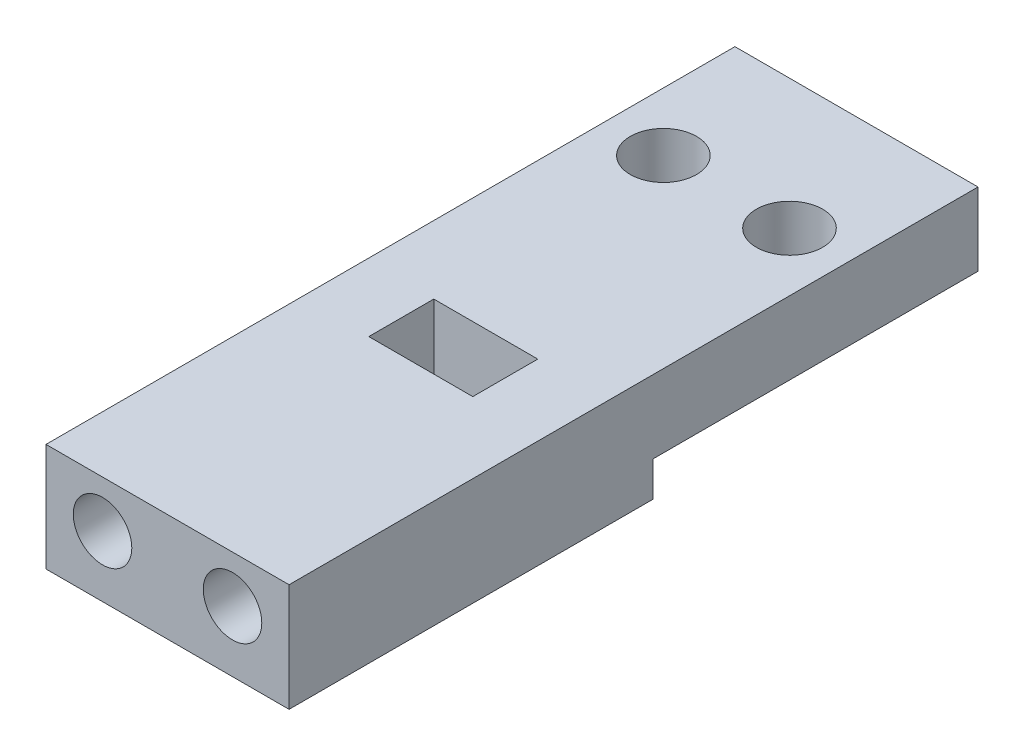
SolidWorks part; units mm, degrees
ref_plane "前视基准面" through (0, 0, 0) normal (0, 0, 1) x (1, 0, 0)
ref_plane "上视基准面" through (0, 0, 0) normal (0, 1, 0) x (1, 0, 0)
ref_plane "右视基准面" through (0, 0, 0) normal (1, 0, 0) x (0, 0, -1)
other "Configuration Table"
sketch "草图1" plane through (0, 0, 0) normal (0, 0, 1) x (1, 0, 0)
  line L1 (-11.1667, -5) -> (11.1667, -5)
  line L2 (-11.1667, -5) -> (-11.1667, 5)
  line L3 (-11.1667, 5) -> (11.1667, 5)
  line L4 (11.1667, -5) -> (11.1667, 5)
  line L5 (-11.1667, -5) -> (11.1667, 5) construction
  line L6 (-11.1667, 5) -> (11.1667, -5) construction
  point P0 (0, 0)
  dimension "D1" = 10
extrude "凸台-拉伸1" add sketch "草图1" along normal blind 30
sketch "草图2" plane through (0, -5, 0) normal (0, -1, 0) x (1, 0, 0)
  line L0 (-10.0833, 30.4566) -> (-10.0833, 0)
  line L1 (-10.0833, 30) -> (-10.0833, 38.1808) construction
  line L2 (-11.1667, 0) -> (11.1667, 0) construction
sketch "草图3" plane through (0, 0, 30) normal (0, 0, 1) x (1, 0, 0)
  line L0 (-9.2333, 0.05) -> (-9.2333, -5.0113)
  line L2 (9.4667, -5) -> (9.4667, 0.05)
  circle A0 centre (5.1167, -0.3) radius 2.25
  circle A1 centre (-4.8833, -0.3) radius 2.25
  arc A3 (9.4667, 0.05) -> (7.4667, 2.05) centre (7.4667, 0.05) ccw
  arc A4 (-9.2333, 0.05) -> (-6.4511, 1.8907) centre (-7.2333, 0.05) cw
sketch "草图4" plane through (0, -5, 0) normal (0, -1, 0) x (1, 0, 0)
  line L1 (-11.1667, 30) -> (-10.0833, 30)
  line L2 (-11.1667, 30) -> (-11.1667, 0)
  line L3 (-11.1667, 0) -> (-10.0833, 0)
  line L4 (-10.0833, 30) -> (-10.0833, 0)
extrude "切除-拉伸1" cut sketch "草图4" against normal blind 30
extrude "切除-拉伸2" cut sketch "草图3" against normal blind 15 contours A1 | A0 region at (-4.8833, -0.3, 30)
sketch "草图5" plane through (0, 0, 30) normal (0, 0, 1) x (1, 0, 0)
  line L0 (9.4667, -5) -> (9.4667, 0.05) construction
  line L1 (-9.2333, -5.0113) -> (9.4667, -5.0113)
  line L2 (-9.2333, -5.0113) -> (-9.2333, 3.3044)
  line L3 (-9.2333, 3.3044) -> (9.4667, 3.3044)
  line L4 (9.4667, -5.0113) -> (9.4667, 3.3044)
extrude "切除-拉伸3" cut sketch "草图5" against normal blind 30 flip side to cut
sketch "草图6" plane through (9.4667, 0, 0) normal (1, 0, 0) x (0, 0, -1)
  line L0 (22.3266, -2.313) -> (13.2059, -2.313) construction
sketch "草图7" plane through (0, 3.3044, 0) normal (0, 1, 0) x (1, 0, 0)
  arc A0 (-18.3547, 13) -> (-15.8066, 10.45) centre (-15.8066, 12.9981) cw
sketch "草图10" plane through (0, 0, 0) normal (0, 0, -1) x (-1, 0, 0)
  line L4 (-9.4667, -5) -> (9.2333, -5)
  line L5 (9.2333, -5) -> (9.2333, 3.3044)
  line L6 (9.2333, 3.3044) -> (-9.4667, 3.3044)
  line L7 (-9.4667, 3.3044) -> (-9.4667, -5)
  line L8 (-9.4667, -5) -> (9.2333, -5)
  line L9 (9.2333, -5) -> (9.2333, 3.3044)
  line L10 (9.2333, 3.3044) -> (-9.4667, 3.3044)
  line L11 (-9.4667, 3.3044) -> (-9.4667, -5)
  dimension "D1" = 0
extrude "凸台-拉伸2" add sketch "草图10" along normal blind 18
sketch "草图11" plane through (9.4667, 0, 0) normal (1, 0, 0) x (0, 0, -1)
  line L1 (18, -5) -> (-2, -5)
  line L2 (18, -5) -> (18, -2.313)
  line L3 (18, -2.313) -> (-2, -2.313)
  line L4 (-2, -5) -> (-2, -2.313)
  dimension "D1" = 20
extrude "切除-拉伸5" cut sketch "草图11" against normal through all
sketch "草图12" plane through (0, -2.313, 0) normal (0, -1, 0) x (1, 0, 0)
  line L0 (-9.2333, -12.9981) -> (9.4667, -12.9981)
  line L1 (-9.2333, -18) -> (-9.2333, 2) construction
  line L2 (9.4667, -200022.3266) -> (9.4667, 199986.7941) construction
  circle A0 centre (-4.7333, -12.9981) radius 2.5481
  circle A1 centre (4.9667, -12.9981) radius 2.5481
  point P5 (-4.7333, -12.9981)
  point P8 (4.9667, -12.9981)
  point P11 (0.1167, -12.9981)
  dimension "D1" = 4.5
  dimension "D2" = 4.5
extrude "切除-拉伸6" cut sketch "草图12" against normal through all contours L0 A0 | L0 A0 | L0 A1 | L0 A1 region at (-4.7333, -2.313, -11.9167) region at (4.9667, -2.313, -11.9167) region at (4.9667, -2.313, -14.0796) region at (-4.7333, -2.313, -14.0796)
sketch "草图13" plane through (0, 3.3044, 0) normal (0, 1, 0) x (1, 0, 0)
  line L0 (-9.2333, 18) -> (-9.2333, -30) construction
  line L1 (9.4667, 18) -> (-9.2333, 18)
  line L2 (9.4667, 18) -> (9.4667, 23)
  line L3 (9.4667, 23) -> (-9.2333, 23)
  line L4 (-9.2333, 18) -> (-9.2333, 23)
extrude "凸台-拉伸3" add sketch "草图13" against normal up to surface (5.6174 mm away) up to face at (-4.7333, -2.313, -15.5463)
sketch "草图14" plane through (0, 3.3044, 0) normal (0, 1, 0) x (1, 0, 0)
  line L1 (-4, -5.4) -> (4, -5.4)
  line L2 (-4, -5.4) -> (-4, -10.4)
  line L3 (-4, -10.4) -> (4, -10.4)
  line L4 (4, -5.4) -> (4, -10.4)
  dimension "D1" = 4
  dimension "D2" = 4
  dimension "D3" = 5.4
  dimension "D4" = 5
extrude "切除-拉伸7" cut sketch "草图14" against normal through all
